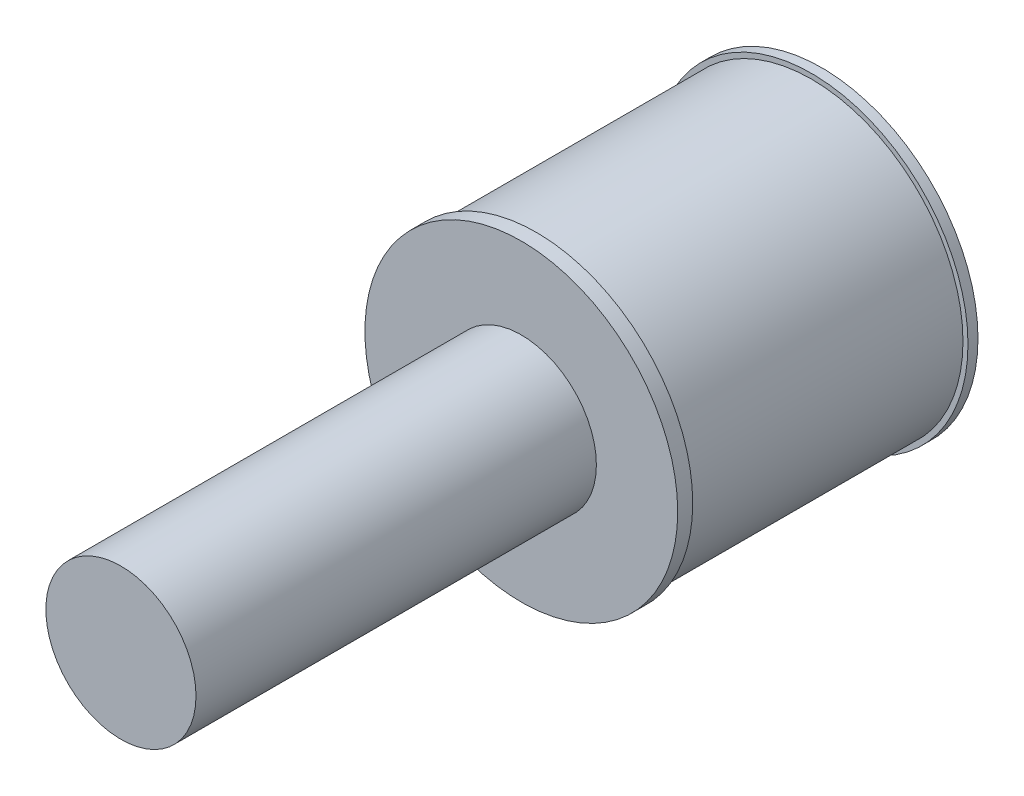
SolidWorks part; units mm, degrees
ref_plane "Front Plane" through (0, 0, 0) normal (0, 0, 1) x (1, 0, 0)
ref_plane "Top Plane" through (0, 0, 0) normal (0, 1, 0) x (1, 0, 0)
ref_plane "Right Plane" through (0, 0, 0) normal (1, 0, 0) x (0, 0, -1)
sketch "S01 - Retaining flange" plane through (0, 0, 0) normal (0, 0, 1) x (1, 0, 0)
  circle A0 centre (0, 0) radius 6.25
  dimension "D1" = 12.5
extrude "01 - Retaining flange" add sketch "S01 - Retaining flange" along normal blind 0.4
sketch "S02 - Inner race and sealed rolling assembly envelope" plane through (0, 0, 0) normal (0, 0, 1) x (1, 0, 0)
  circle A0 centre (0, 0) radius 6.05
  dimension "D1" = 12.1
extrude "02 - Inner race and sealed rolling assembly envelope" add sketch "S02 - Inner race and sealed rolling assembly envelope" along normal blind 11 from offset 0.4
sketch "S03 - Mounting thrust face" plane through (0, 0, 0) normal (0, 0, 1) x (1, 0, 0)
  circle A0 centre (0, 0) radius 6.25
  dimension "D1" = 12.5
extrude "03 - Mounting thrust face" add sketch "S03 - Mounting thrust face" along normal blind 0.6 from offset 11.4
sketch "S04 - Six millimetre stud with final 8 mm M6 thread envelope" plane through (0, 0, 0) normal (0, 0, 1) x (1, 0, 0)
  circle A0 centre (0, 0) radius 3
  dimension "D1" = 6
extrude "04 - Six millimetre stud with final 8 mm M6 thread envelope" add sketch "S04 - Six millimetre stud with final 8 mm M6 thread envelope" along normal blind 16 from offset 12
sketch "S05 - Assembly drive slot" plane through (0, 0, 0) normal (0, 0, 1) x (1, 0, 0)
  line L0 (-4.2, -0.7) -> (4.2, -0.7)
  line L1 (4.2, -0.7) -> (4.2, 0.7)
  line L2 (4.2, 0.7) -> (-4.2, 0.7)
  line L3 (-4.2, 0.7) -> (-4.2, -0.7)
  dimension "D1" = 4.2
  dimension "D2" = 4.2
  dimension "D3" = 0.7
  dimension "D4" = 0.7
extrude "05 - Assembly drive slot" cut sketch "S05 - Assembly drive slot" along normal blind 0.7 from offset 0.1 offset against normal yes
